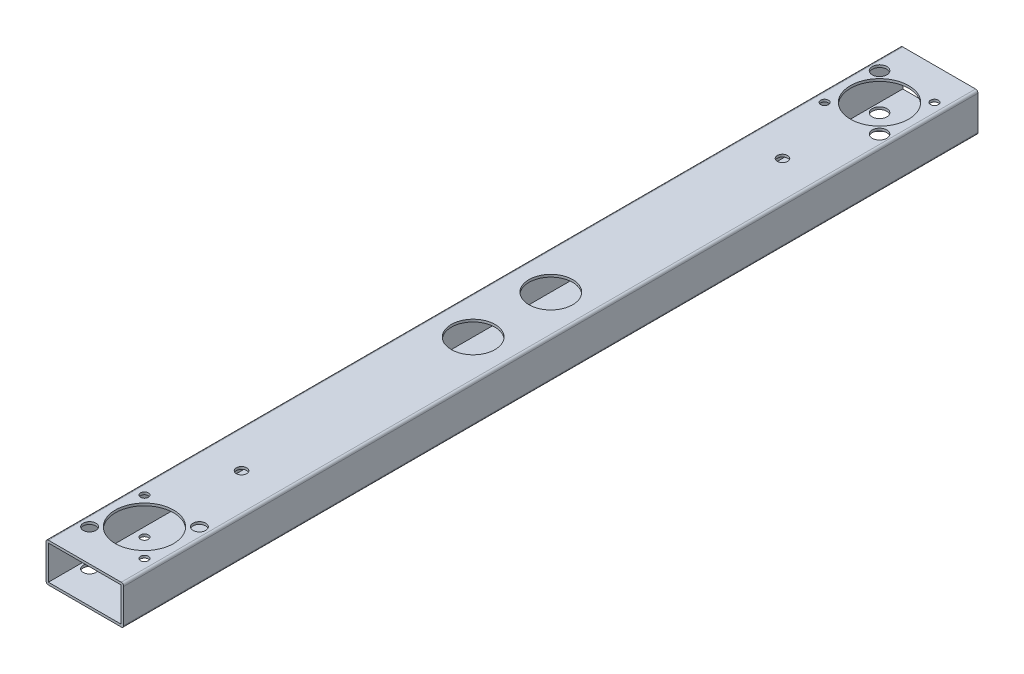
SolidWorks part; units mm, degrees
ref_plane "Front Plane" through (0, 0, 0) normal (0, 0, 1) x (1, 0, 0)
ref_plane "Top Plane" through (0, 0, 0) normal (0, 1, 0) x (1, 0, 0)
ref_plane "Right Plane" through (0, 0, 0) normal (1, 0, 0) x (0, 0, -1)
sketch "Sketch1" plane through (0, 0, 0) normal (0, 0, 1) x (1, 0, 0)
  line L0 (-23.8125, 11.1125) -> (23.8125, 11.1125)
  line L1 (-23.8125, -12.7) -> (23.8125, -12.7)
  line L2 (-25.4, -11.1125) -> (-25.4, 11.1125)
  line L3 (-23.8125, 12.7) -> (23.8125, 12.7)
  line L4 (25.4, -11.1125) -> (25.4, 11.1125)
  line L5 (-25.4, -12.7) -> (25.4, 12.7) construction
  line L6 (-25.4, 12.7) -> (25.4, -12.7) construction
  line L7 (23.8125, -11.1125) -> (23.8125, 11.1125)
  line L8 (-23.8125, -11.1125) -> (23.8125, -11.1125)
  line L9 (-23.8125, -11.1125) -> (-23.8125, 11.1125)
  line L10 (-25.4, -12.7) -> (25.4, -12.7) construction
  line L11 (-25.4, -12.7) -> (-25.4, 12.7) construction
  line L12 (25.4, -12.7) -> (25.4, 12.7) construction
  line L13 (-25.4, 12.7) -> (25.4, 12.7) construction
  arc A0 (-23.8125, -12.7) -> (-25.4, -11.1125) centre (-23.8125, -11.1125) cw
  arc A1 (23.8125, -12.7) -> (25.4, -11.1125) centre (23.8125, -11.1125) ccw
  arc A2 (23.8125, 12.7) -> (25.4, 11.1125) centre (23.8125, 11.1125) cw
  arc A3 (-25.4, 11.1125) -> (-23.8125, 12.7) centre (-23.8125, 11.1125) cw
  point P0 (0, 0)
  dimension "D4" = 1.5875
  dimension "D1" = 25.4
  dimension "D2" = 50.8
  dimension "D3" = 1.5875
extrude "Boss-Extrude1" add sketch "Sketch1" along normal blind 558.8
sketch "Sketch2" plane through (0, 12.7, 0) normal (0, 1, 0) x (1, 0, 0)
  line L2 (0, -519.8) -> (0, -304.8) construction
  line L3 (0, -304.8) -> (0, -254) construction
  line L4 (0, -254) -> (0, -39) construction
  line L5 (0, -519.8) -> (0, -558.8) construction
  line L6 (23.8125, -558.8) -> (-23.8125, -558.8) construction
  line L7 (0, -39) -> (0, 0) construction
  line L8 (23.8125, 0) -> (-23.8125, 0) construction
  circle A8 centre (0, -519.8) radius 19.05
  circle A9 centre (0, -304.8) radius 14.2875
  circle A10 centre (0, -254) radius 14.2875
  circle A11 centre (0, -39) radius 19.05
  point P7 (0, -254.2607)
  dimension "D1" = 38.1
  dimension "D4" = 215
  dimension "D2" = 28.575
  dimension "D3" = 50.8
extrude "Cut-Extrude1" cut sketch "Sketch2" against normal up to next and the other way through all
sketch "Sketch3" plane through (0, -12.7, 0) normal (0, -1, 0) x (1, 0, 0)
  circle A0 centre (0, 39) radius 12.7
  circle A1 centre (0, 254) radius 12.7
  circle A2 centre (0, 304.8) radius 12.7
  circle A3 centre (0, 519.8) radius 12.7
  circle A4 centre (0, 519.8) radius 19.05 construction
  circle A6 centre (0, 304.8) radius 14.2875 construction
  circle A7 centre (0, 254) radius 14.2875 construction
  circle A8 centre (0, 39) radius 19.05 construction
  dimension "D1" = 25.4
  dimension "D2" = 25.4
extrude "Cut-Extrude2" cut sketch "Sketch3" against normal up to next and the other way through all
sketch "Sketch7" plane through (0, 11.1125, 0) normal (0, -1, 0) x (1, 0, 0)
  arc A0 (-15.4078, 501.8395) -> (-20.5132, 501.8395) centre (-17.9605, 501.8395) ccw construction
  arc A1 (-20.5132, 501.8395) -> (-15.4078, 501.8395) centre (-17.9605, 501.8395) ccw construction
  arc A2 (15.4078, 537.7605) -> (20.5132, 537.7605) centre (17.9605, 537.7605) ccw construction
  arc A3 (20.5132, 537.7605) -> (15.4078, 537.7605) centre (17.9605, 537.7605) ccw construction
  arc A4 (-15.4078, 501.8395) -> (-20.5132, 501.8395) centre (-17.9605, 501.8395) ccw
  arc A5 (-20.5132, 501.8395) -> (-15.4078, 501.8395) centre (-17.9605, 501.8395) ccw
  arc A6 (15.4078, 537.7605) -> (20.5132, 537.7605) centre (17.9605, 537.7605) ccw
  arc A7 (20.5132, 537.7605) -> (15.4078, 537.7605) centre (17.9605, 537.7605) ccw
  arc A16 (20.5132, 21.0395) -> (15.4078, 21.0395) centre (17.9605, 21.0395) ccw construction
  arc A17 (15.4078, 21.0395) -> (20.5132, 21.0395) centre (17.9605, 21.0395) ccw construction
  arc A18 (-15.4078, 56.9605) -> (-20.5132, 56.9605) centre (-17.9605, 56.9605) ccw construction
  arc A19 (-20.5132, 56.9605) -> (-15.4078, 56.9605) centre (-17.9605, 56.9605) ccw construction
  arc A20 (20.5132, 21.0395) -> (15.4078, 21.0395) centre (17.9605, 21.0395) ccw
  arc A21 (15.4078, 21.0395) -> (20.5132, 21.0395) centre (17.9605, 21.0395) ccw
  arc A22 (-15.4078, 56.9605) -> (-20.5132, 56.9605) centre (-17.9605, 56.9605) ccw
  arc A23 (-20.5132, 56.9605) -> (-15.4078, 56.9605) centre (-17.9605, 56.9605) ccw
  arc A24 (20.5132, 501.8395) -> (15.4078, 501.8395) centre (17.9605, 501.8395) ccw construction
  arc A25 (15.4078, 501.8395) -> (20.5132, 501.8395) centre (17.9605, 501.8395) ccw construction
  arc A26 (-20.4965, 537.9028) -> (-15.4245, 537.6183) centre (-17.9605, 537.7605) ccw construction
  arc A27 (-15.4078, 537.7605) -> (-20.5132, 537.7605) centre (-17.9605, 537.7605) ccw construction
  arc A28 (20.5132, 501.8395) -> (15.4078, 501.8395) centre (17.9605, 501.8395) ccw construction
  arc A29 (15.4078, 501.8395) -> (20.5132, 501.8395) centre (17.9605, 501.8395) ccw construction
  arc A30 (-20.4965, 537.9028) -> (-15.4245, 537.6183) centre (-17.9605, 537.7605) ccw construction
  arc A31 (-15.4078, 537.7605) -> (-20.5132, 537.7605) centre (-17.9605, 537.7605) ccw construction
  arc A32 (-15.4078, 21.0395) -> (-20.5132, 21.0395) centre (-17.9605, 21.0395) ccw construction
  arc A33 (-20.5132, 21.0395) -> (-15.4078, 21.0395) centre (-17.9605, 21.0395) ccw construction
  arc A34 (15.4078, 56.9605) -> (20.5132, 56.9605) centre (17.9605, 56.9605) ccw construction
  arc A35 (20.5132, 56.9605) -> (15.4078, 56.9605) centre (17.9605, 56.9605) ccw construction
  arc A36 (-15.4078, 21.0395) -> (-20.5132, 21.0395) centre (-17.9605, 21.0395) ccw construction
  arc A37 (-20.5132, 21.0395) -> (-15.4078, 21.0395) centre (-17.9605, 21.0395) ccw construction
  arc A38 (15.4078, 56.9605) -> (20.5132, 56.9605) centre (17.9605, 56.9605) ccw construction
  arc A39 (20.5132, 56.9605) -> (15.4078, 56.9605) centre (17.9605, 56.9605) ccw construction
  circle A40 centre (17.9605, 56.9605) radius 4.7625
  circle A41 centre (-17.9605, 21.0395) radius 4.7625
  circle A42 centre (17.9605, 501.8395) radius 4.1402
  circle A43 centre (-17.9605, 537.7605) radius 4.1402
  dimension "D1" = 1.5875
  dimension "D2" = 9.525
extrude "Cut-Extrude3" cut sketch "Sketch7" against normal through all and the other way through all
sketch "Sketch8" plane through (0, 12.7, 0) normal (0, 1, 0) x (1, 0, 0)
  line L0 (0, -39) -> (0, -254) construction
  line L1 (0, -304.8) -> (0, -519.8) construction
  circle A0 centre (0, -102.5) radius 3.3782
  circle A1 centre (0, -456.3) radius 3.3782
  point P12 (-6.259, -105.8621)
  point P13 (0, 0)
  dimension "D1" = 6.7564
  dimension "D2" = 63.5
  dimension "D3" = 63.5
extrude "Cut-Extrude4" cut sketch "Sketch8" against normal up to next and the other way through all
sketch "Sketch9" plane through (0, -12.7, 0) normal (0, -1, 0) x (1, 0, 0)
  line L0 (0, 39) -> (0, 254) construction
  line L1 (0, 304.8) -> (0, 519.8) construction
  circle A0 centre (0, 102.5) radius 7.9375
  circle A1 centre (0, 456.3) radius 7.9375
  circle A2 centre (0, 102.5) radius 3.3782 construction
  circle A3 centre (0, 456.3) radius 3.3782 construction
  dimension "D1" = 15.875
extrude "Cut-Extrude5" cut sketch "Sketch9" against normal up to next and the other way through all
